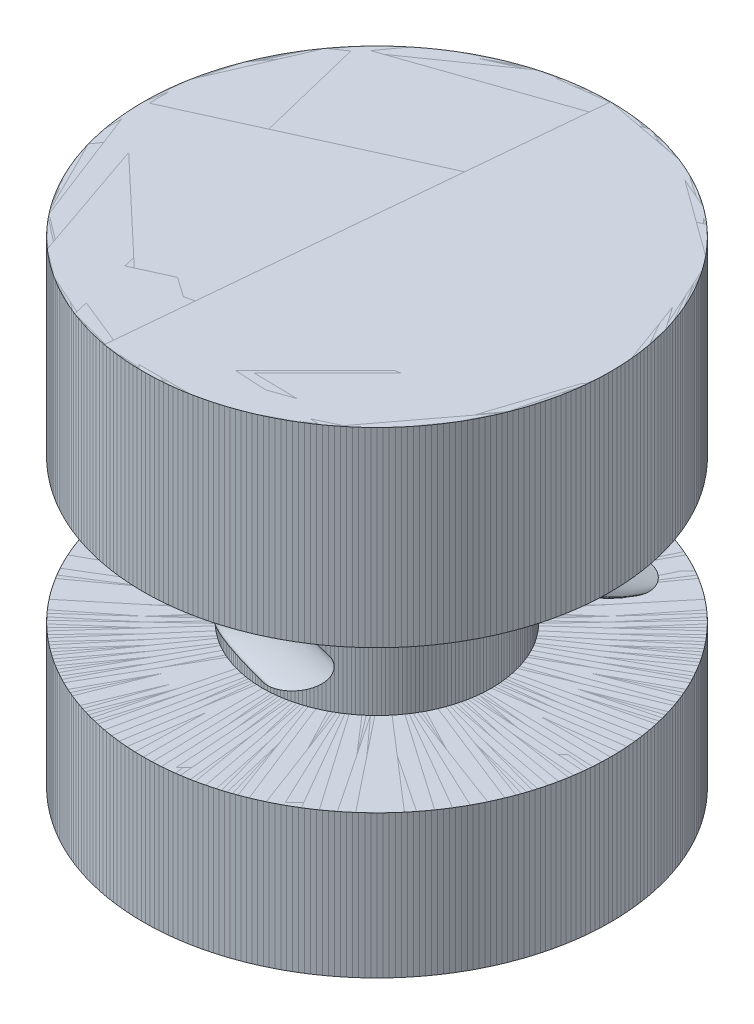
SolidWorks part; units mm, degrees
ref_plane "Front Plane" through (0, 0, 0) normal (0, 0, 1) x (1, 0, 0)
ref_plane "Top Plane" through (0, 0, 0) normal (0, 1, 0) x (1, 0, 0)
ref_plane "Right Plane" through (0, 0, 0) normal (1, 0, 0) x (0, 0, -1)
sketch "Sketch1" plane through (0, 0, 0) normal (0, 0, 1) x (1, 0, 0)
  line L0 (0, 0) -> (6.223, 0)
  line L1 (6.223, 0) -> (6.223, -5.08)
  line L2 (6.223, -5.08) -> (3.048, -5.08)
  line L3 (3.048, -5.08) -> (3.048, -8.89)
  line L4 (3.048, -8.89) -> (6.223, -8.89)
  line L5 (6.223, -8.89) -> (6.223, -12.7)
  line L6 (6.223, -12.7) -> (0, -12.7)
  line L7 (0, -12.7) -> (0, 0)
  dimension "D1" = 12.7
  dimension "D2" = 3.81
  dimension "D3" = 3.81
  dimension "D4" = 6.223
  dimension "D5" = 3.048
  dimension "D6" = 6.223
revolve "button body" add sketch "Sketch1" angle 360 about L7
ref_plane "spring path" through (4.318, 0, 0) normal (1, 0, 0) x (0, 0, -1)
sketch "Sketch2" plane through (4.318, 0, 0) normal (1, 0, 0) x (0, 0, -1)
  spline S0 degree 3 poles (2.9542, -4.563) (1.8538, -5.2739) (-1.4839, -5.7786) (3.0242, -6.9827) knots 0 0 0 0 1 1 1 1
ref_plane "spring cross section" through (0, 0, -3.0242) normal (0, 0, 1) x (1, 0, 0)
sketch "Sketch4" plane through (0, 0, -3.0242) normal (0, 0, 1) x (1, 0, 0)
  ellipse E0 centre (4.318, -6.9827) end of major axis (3.556, -6.9827) minor radius 0.2032
  dimension "D1" = 0
sweep "spring" add profiles "Sketch4" path "Sketch2"
ref_axis "center axis" through (0, 0, 0) along (0, -1, 0)
pattern_circular "moar springs" count 4 over 360 about axis through (0, 0, 0) along (0, -1, 0) of bodies 102
ref_plane "spring cutoff" through (0, -6.731, 0) normal (0, 1, 0) x (1, 0, 0)
sketch "Sketch5" plane through (0, -6.731, 0) normal (0, 1, 0) x (1, 0, 0)
  line L1 (-5.4573, -1.4157) -> (-3.0941, -1.4157)
  line L2 (-5.4573, -1.4157) -> (-5.4573, -3.506)
  line L3 (-5.4573, -3.506) -> (-3.0941, -3.506)
  line L4 (-3.0941, -1.4157) -> (-3.0941, -3.506)
  line L5 (1.4555, -3.3381) -> (3.3946, -3.3381)
  line L6 (1.4555, -3.3381) -> (1.4555, -5.4537)
  line L7 (1.4555, -5.4537) -> (3.3946, -5.4537)
  line L8 (3.3946, -3.3381) -> (3.3946, -5.4537)
  line L9 (3.3946, 3.1587) -> (5.2632, 3.1587)
  line L10 (3.3946, 3.1587) -> (3.3946, 1.2698)
  line L11 (3.3946, 1.2698) -> (5.2632, 1.2698)
  line L12 (5.2632, 3.1587) -> (5.2632, 1.2698)
  line L13 (-3.4934, 5.5558) -> (-1.1945, 5.5558)
  line L14 (-3.4934, 5.5558) -> (-3.4934, 3.1587)
  line L15 (-3.4934, 3.1587) -> (-1.1945, 3.1587)
  line L16 (-1.1945, 5.5558) -> (-1.1945, 3.1587)
extrude "flatten springs" cut sketch "Sketch5" along direction (0, 1, 0) on the side against the normal up to surface (2.159 mm away) up to face at (-3.048, -8.89, 0)
